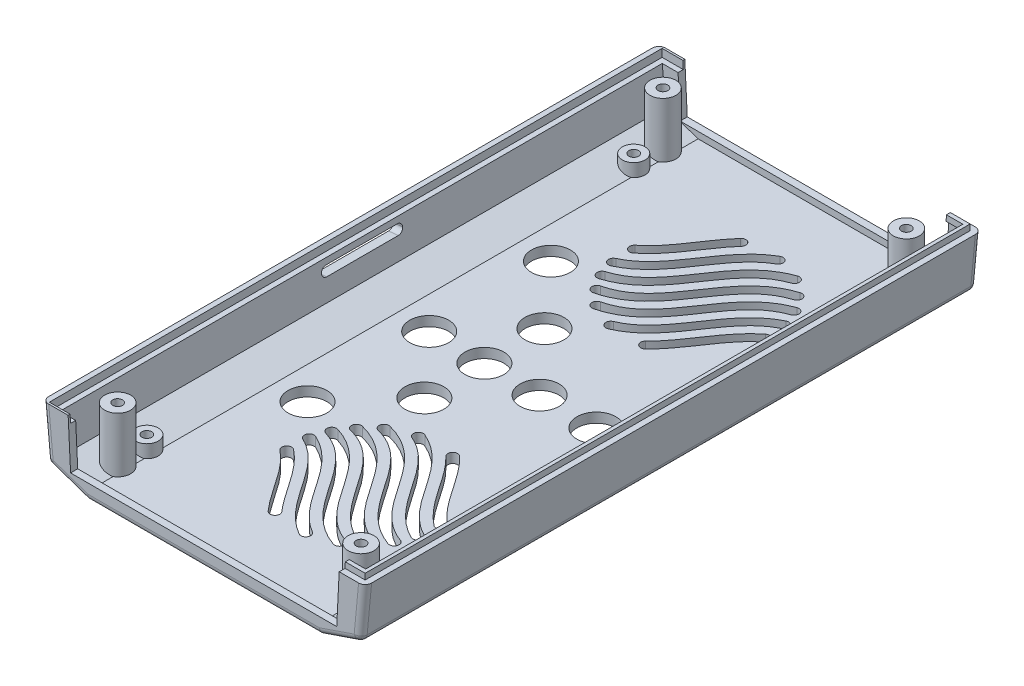
SolidWorks part; units mm, degrees
ref_plane "Спереди" through (0, 0, 0) normal (0, 0, 1) x (1, 0, 0)
ref_plane "Сверху" through (0, 0, 0) normal (0, 1, 0) x (1, 0, 0)
ref_plane "Справа" through (0, 0, 0) normal (1, 0, 0) x (0, 0, -1)
sketch "Эскиз1" plane through (0, 0, 0) normal (0, 0, 1) x (1, 0, 0)
  line L0 (-48.25, 4.1905) -> (-35.9646, 0)
  line L1 (48.25, 4.1905) -> (49.75, 20)
  line L2 (-48.25, 4.1905) -> (-49.75, 20)
  line L3 (-35.9646, 0) -> (35.9646, 0)
  line L4 (35.9646, 0) -> (48.25, 4.1905)
  line L5 (-49.75, 20) -> (49.75, 20) construction
  line L6 (45.4465, 6.404) -> (46.7634, 20.2834)
  line L7 (35.4671, 3) -> (45.4465, 6.404)
  line L8 (-35.4671, 3) -> (35.4671, 3)
  line L9 (-45.4465, 6.404) -> (-35.4671, 3)
  line L10 (-45.4465, 6.404) -> (-46.5088, 17.6)
  line L11 (49.75, 20) -> (47.95, 20)
  line L12 (47.95, 20) -> (47.95, 21.8)
  line L13 (46.7634, 20.2834) -> (46.9073, 21.8)
  line L14 (46.9073, 21.8) -> (47.95, 21.8)
  line L15 (-49.75, 20) -> (-48.15, 20)
  line L16 (-48.15, 20) -> (-48.15, 17.6)
  line L17 (-48.15, 17.6) -> (-46.5088, 17.6)
  line L20 (-45.4465, 6.404) -> (-46.7634, 20.2834) construction
  point P3 (0, 0)
  point P5 (0, 20)
  dimension "D1" = 99.5
  dimension "D2" = 20
  dimension "D3" = 96.5
  dimension "D4" = 3
  dimension "D5" = 1.8
  dimension "D6" = 1.8
  dimension "D7" = 2.4
  dimension "D8" = 1.6
extrude "Бобышка-Вытянуть1" add sketch "Эскиз1" along normal blind 92.8 and the other way blind 92.8
ref_plane "Плоскость смыкания" through (0, 20, 0) normal (0, 1, 0) x (-1, 0, 0)
ref_plane "Плоскость2" through (0, 0, -92.8) normal (0, 0, 1) x (1, 0, 0)
ref_plane "Плоскость3" through (0, 0, 92.8) normal (0, 0, 1) x (1, 0, 0)
ref_plane "Плоскость4" through (0, 3, 0) normal (0, 1, 0) x (-1, 0, 0)
sketch "Эскиз5" plane through (0, 0, 92.8) normal (0, 0, 1) x (1, 0, 0)
  line L0 (-48.25, 4.1905) -> (-35.9646, 0)
  line L1 (48.25, 4.1905) -> (49.75, 20)
  line L2 (-48.25, 4.1905) -> (-49.75, 20)
  line L3 (-35.9646, 0) -> (35.9646, 0)
  line L4 (35.9646, 0) -> (48.25, 4.1905)
  line L5 (-48.15, 20) -> (47.95, 20)
  line L11 (49.75, 20) -> (47.95, 20)
  line L15 (-49.75, 20) -> (-48.15, 20)
  point P3 (0, 0)
  point P6 (45.4465, 6.404)
  point P10 (46.7634, 20.2834)
  point P13 (-45.4465, 6.404)
  point P14 (-46.7634, 20.2834)
extrude "Бобышка-Вытянуть3" add sketch "Эскиз5" along normal blind 2.2
sketch "Эскиз9" plane through (0, 20, 0) normal (0, 1, 0) x (-1, 0, 0)
  line L0 (48.15, -92.8) -> (48.15, 92.8) construction
  line L1 (48.15, 92.8) -> (38.4865, 92.8)
  line L2 (48.15, 92.8) -> (48.15, 94.4)
  line L3 (48.15, 94.4) -> (38.4865, 94.4)
  line L4 (38.4865, 92.8) -> (38.4865, 94.4)
  dimension "D1" = 1.6
extrude "Вырез-Вытянуть3" cut sketch "Эскиз9" against normal blind 2.4
sketch "Эскиз10" plane through (0, 20, 0) normal (0, 1, 0) x (1, 0, 0)
  line L1 (47.95, -92) -> (32.5393, -92)
  line L2 (47.95, -92) -> (47.95, -93.2)
  line L3 (47.95, -93.2) -> (32.5393, -93.2)
  line L4 (32.5393, -92) -> (32.5393, -93.2)
  line L5 (47.95, 92.8) -> (47.95, -92.8) construction
  line L6 (47.95, 92.8) -> (47.95, -92.8) construction
  dimension "D1" = 1.2
extrude "Бобышка-Вытянуть4" add sketch "Эскиз10" along normal blind 1.8
sketch "Эскиз6" plane through (0, 0, 95) normal (0, 0, 1) x (1, 0, 0)
  line L0 (-41.75, 19.9919) -> (-41, 4.9919)
  line L2 (-41, 4.9919) -> (41, 4.9919)
  line L3 (41, 4.9919) -> (41.75, 19.9919)
  line L4 (41.75, 19.9919) -> (41.8404, 21.8)
  line L6 (32.5393, 21.8) -> (47.95, 21.8) construction
  line L7 (41.8404, 21.8) -> (-41.75, 21.8)
  line L8 (-41.75, 21.8) -> (-41.75, 19.9919)
  point P4 (0, 19.9919)
  point P7 (0, 4.9919)
  dimension "D1" = 83.5
  dimension "D2" = 82
  dimension "D3" = 15
extrude "Вырез-Вытянуть1" cut sketch "Эскиз6" against normal blind 3
mirror "Зеркальное отражение2" about plane through (0, 0, 0) normal (0, 0, 1) of "Вырез-Вытянуть1", "Бобышка-Вытянуть3", "Вырез-Вытянуть3", "Бобышка-Вытянуть4"
fillet "Скругление1" radius 2 12 edges at (48.25, 4.1905, 0) (-48.25, 4.1905, 0) (49, 12.0952, 95) (42.1073, 2.0952, 95) (0, 0, 95) (-42.1073, 2.0952, 95) (-49, 12.0952, 95) (-49, 12.0952, -95) (-42.1073, 2.0952, -95) (0, 0, -95) (42.1073, 2.0952, -95) (49, 12.0952, -95)
sketch "Эскиз12" plane through (0, 20, 0) normal (0, 1, 0) x (-1, 0, 0)
  circle A0 centre (37.5, -84) radius 4
  circle A1 centre (37.5, 84) radius 4
  circle A2 centre (-37.5, 84) radius 4
  circle A3 centre (-37.5, -84) radius 4
  circle A4 centre (37.5, -84) radius 1.5
  circle A5 centre (-37.5, -84) radius 1.5
  circle A6 centre (-37.5, 84) radius 1.5
  circle A7 centre (37.5, 84) radius 1.5
  dimension "D1" = 84
  dimension "D2" = 84
  dimension "D3" = 37.5
  dimension "D4" = 37.5
extrude "Бобышка-Вытянуть5" add sketch "Эскиз12" against normal blind 17
sketch "Эскиз13" plane through (0, 3, 0) normal (0, 1, 0) x (-1, 0, 0)
  circle A0 centre (37.5, -75) radius 3.5
  circle A1 centre (-37.5, -75) radius 3.5
  circle A2 centre (-37.5, 75) radius 3.5
  circle A3 centre (37.5, 75) radius 3.5
  circle A4 centre (37.5, -75) radius 1.5
  circle A5 centre (-37.5, -75) radius 1.5
  circle A6 centre (-37.5, 75) radius 1.5
  circle A7 centre (37.5, 75) radius 1.5
  dimension "D1" = 37.5
  dimension "D2" = 37.5
  dimension "D3" = 75
  dimension "D4" = 75
extrude "Бобышка-Вытянуть6" add sketch "Эскиз13" along normal blind 4
sketch "Эскиз14" plane through (-47.4255, -4.4997, 0) normal (-0.9955, -0.0945, 0) x (0, 0, 1)
  line L0 (-12.5, 18.6097) -> (12.5, 18.5897) construction
  line L1 (-11.01, 20.0997) -> (11.01, 20.0997)
  line L2 (-12.5, 18.6097) -> (-12.5, 18.5897)
  line L3 (-11.01, 17.0997) -> (11.01, 17.0997)
  line L4 (12.5, 18.6097) -> (12.5, 18.5897)
  line L5 (-93, 24.6097) -> (93, 24.6097) construction
  line L6 (0, 20.0997) -> (0, 17.0997) construction
  arc A0 (11.01, 20.0997) -> (12.5, 18.6097) centre (11.01, 18.6097) cw
  arc A1 (12.5, 18.5897) -> (11.01, 17.0997) centre (11.01, 18.5897) cw
  arc A2 (-11.01, 17.0997) -> (-12.5, 18.5897) centre (-11.01, 18.5897) cw
  arc A3 (-11.01, 20.0997) -> (-12.5, 18.6097) centre (-11.01, 18.6097) ccw
  point P4 (0, 17.0997)
  point P8 (12.5, 20.0997)
  point P13 (-12.5, 17.0997)
  point P16 (-12.5, 20.0997)
  point P19 (0, 24.6097)
  dimension "D3" = 1.49
  dimension "D1" = 25
  dimension "D2" = 3
  dimension "D4" = 6
extrude "Вырез-Вытянуть4" cut sketch "Эскиз14" against normal blind 3
sketch "Эскиз23" plane through (0, 0, 0) normal (0, -1, 0) x (1, 0, 0)
  line L0 (0, -93) -> (0, 93) construction
  line L1 (-35.9646, -93) -> (35.9646, -93) construction
  line L2 (35.9646, 93) -> (-35.9646, 93) construction
  line L3 (-49.75, 0) -> (49.75, 0) construction
  line L6 (-49.75, -93) -> (-49.75, 93) construction
  line L7 (49.75, -93) -> (49.75, 93) construction
  point P12 (0, 0)
sketch "Эскиз27" plane through (-36.5202, 0, -3.5105) normal (0, -1, 0) x (0, 0, 1)
  line L0 (3.5105, 0.9798) -> (3.5105, -74.0202) construction
  line L1 (-71.4995, -36.5202) -> (78.885, -36.5202) construction
  circle A0 centre (22.0105, -28.0202) radius 6
  circle A1 centre (-33.9895, -11.0202) radius 6
  circle A2 centre (3.5105, -11.0202) radius 6
  circle A3 centre (41.0105, -11.0202) radius 6
  circle A4 centre (54.5105, -42.5202) radius 25 construction
  circle A5 centre (-14.9895, -28.0202) radius 6
  circle A6 centre (3.5105, -28.0202) radius 6
  circle A7 centre (3.5105, -45.0202) radius 6
  circle A8 centre (3.5105, -62.5202) radius 6
  circle A9 centre (-47.4895, -42.5202) radius 25 construction
  arc A10 (-48.8656, -21.59) -> (-51.2327, -19.7469) centre (-50.0492, -20.6685) ccw
  arc A11 (-44.7101, -20.2817) -> (-41.9906, -21.5484) centre (-43.3503, -20.915) cw
  arc A12 (-39.5591, -22.1707) -> (-36.6947, -23.0625) centre (-38.1269, -22.6166) cw
  arc A13 (-34.9969, -25.2662) -> (-32.0843, -25.9852) centre (-33.5406, -25.6257) cw
  arc A14 (-30.7542, -29.5088) -> (-27.8417, -30.2278) centre (-29.298, -29.8683) cw
  arc A15 (-27.5032, -36.7235) -> (-24.7455, -37.9047) centre (-26.1244, -37.3141) cw
  arc A16 (-27.2708, -46.9318) -> (-25.0975, -48.9998) centre (-26.1841, -47.9658) cw
  arc A17 (-69.2669, -34.1546) -> (-67.2799, -36.4022) centre (-68.2734, -35.2784) ccw
  arc A18 (-70.5617, -45.0109) -> (-67.9586, -46.5021) centre (-69.2602, -45.7565) ccw
  arc A19 (-68.0072, -52.9601) -> (-65.174, -53.9464) centre (-66.5906, -53.4532) ccw
  arc A20 (-63.9746, -57.836) -> (-61.1135, -58.7384) centre (-62.544, -58.2872) ccw
  arc A21 (-59.4766, -61.3164) -> (-56.6494, -62.32) centre (-58.063, -61.8182) ccw
  arc A22 (-54.2329, -63.1869) -> (-51.5421, -64.5135) centre (-52.8875, -63.8502) ccw
  arc A23 (-47.5717, -63.5739) -> (-45.1994, -65.4101) centre (-46.3856, -64.492) ccw
  arc A24 (58.2537, -19.7469) -> (55.8866, -21.59) centre (57.0701, -20.6685) ccw
  arc A25 (49.0116, -21.5484) -> (51.731, -20.2817) centre (50.3713, -20.915) cw
  arc A26 (43.7157, -23.0625) -> (46.5801, -22.1707) centre (45.1479, -22.6166) cw
  arc A27 (39.1053, -25.9852) -> (42.0179, -25.2662) centre (40.5616, -25.6257) cw
  arc A28 (34.8627, -30.2278) -> (37.7752, -29.5088) centre (36.3189, -29.8683) cw
  arc A29 (31.7665, -37.9047) -> (34.5242, -36.7235) centre (33.1454, -37.3141) cw
  arc A30 (32.1184, -48.9998) -> (34.2918, -46.9318) centre (33.2051, -47.9658) cw
  arc A31 (76.2879, -34.1546) -> (74.3009, -36.4022) centre (75.2944, -35.2784) cw
  arc A32 (77.5827, -45.0109) -> (74.9796, -46.5021) centre (76.2811, -45.7565) cw
  arc A33 (75.0282, -52.9601) -> (72.1949, -53.9464) centre (73.6116, -53.4532) cw
  arc A34 (70.9955, -57.836) -> (68.1345, -58.7384) centre (69.565, -58.2872) cw
  arc A35 (66.4976, -61.3164) -> (63.6704, -62.32) centre (65.084, -61.8182) cw
  arc A36 (61.2539, -63.1869) -> (58.5631, -64.5135) centre (59.9085, -63.8502) cw
  arc A37 (54.5927, -63.5739) -> (52.2203, -65.4101) centre (53.4065, -64.492) cw
  spline S0 degree 3 poles (-62.544, -58.2872) (-57.6134, -42.6538) (-37.566, -41.9323) (-33.5406, -25.6257) knots 0 0 0 0 1 1 1 1 construction
  spline S1 degree 3 poles (-66.5906, -53.4532) (-64.9753, -48.8132) (-58.5281, -41.6719) (-45.7936, -34.5728) (-39.5897, -27.3147) (-38.1269, -22.6166) knots 0.012762 0.012762 0.012762 0.012762 0.316872 0.671472 0.974157 0.974157 0.974157 0.974157 construction
  spline S2 degree 3 poles (-69.2602, -45.7565) (-67.5896, -42.8402) (-61.6924, -36.8281) (-50.7993, -30.7556) (-44.9391, -24.3259) (-43.3503, -20.915) knots 0.094171 0.094171 0.094171 0.094171 0.316872 0.671472 0.916546 0.916546 0.916546 0.916546 construction
  spline S3 degree 3 poles (-68.2734, -35.2784) (-67.8647, -34.917) (-63.4796, -31.2167) (-56.4359, -27.29) (-51.3026, -22.2782) (-50.0492, -20.6685) knots 0.27954 0.27954 0.27954 0.27954 0.316872 0.671472 0.811315 0.811315 0.811315 0.811315 construction
  spline S4 degree 3 poles (-58.063, -61.8182) (-56.4384, -57.2414) (-46.7878, -46.5806) (-32.0478, -41.0078) (-29.298, -29.8683) knots 0.015397 0.015397 0.015397 0.015397 0.316872 1 1 1 1 construction
  spline S5 degree 3 poles (53.4065, -64.492) (52.0058, -62.6823) (46.6132, -57.5469) (38.7406, -53.1581) (34.0451, -48.8486) (33.2051, -47.9658) knots 0.161129 0.161129 0.161129 0.161129 0.316872 0.671472 0.755481 0.755481 0.755481 0.755481 construction
  spline S6 degree 3 poles (59.9085, -63.8502) (58.2051, -60.395) (52.1118, -54.0044) (40.6708, -47.6263) (34.7264, -41.0056) (33.1454, -37.3141) knots 0.066312 0.066312 0.066312 0.066312 0.316872 0.671472 0.930061 0.930061 0.930061 0.930061 construction
  spline S7 degree 3 poles (-52.8875, -63.8502) (-51.1841, -60.395) (-45.0908, -54.0044) (-33.6498, -47.6263) (-27.7054, -41.0056) (-26.1244, -37.3141) knots 0.066312 0.066312 0.066312 0.066312 0.316872 0.671472 0.930061 0.930061 0.930061 0.930061 construction
  spline S8 degree 3 poles (-46.3856, -64.492) (-44.9848, -62.6823) (-39.5922, -57.5469) (-31.7196, -53.1581) (-27.0241, -48.8486) (-26.1841, -47.9658) knots 0.161129 0.161129 0.161129 0.161129 0.316872 0.671472 0.755481 0.755481 0.755481 0.755481 construction
  spline S9 degree 3 poles (65.084, -61.8182) (63.4594, -57.2414) (53.8088, -46.5806) (39.0688, -41.0078) (36.3189, -29.8683) knots 0.015397 0.015397 0.015397 0.015397 0.316872 1 1 1 1 construction
  spline S10 degree 3 poles (69.565, -58.2872) (64.6344, -42.6538) (44.5869, -41.9323) (40.5616, -25.6257) knots 0 0 0 0 1 1 1 1 construction
  spline S11 degree 3 poles (73.6116, -53.4532) (71.9963, -48.8132) (65.549, -41.6719) (52.8146, -34.5728) (46.6107, -27.3147) (45.1479, -22.6166) knots 0.012762 0.012762 0.012762 0.012762 0.316872 0.671472 0.974157 0.974157 0.974157 0.974157 construction
  spline S12 degree 3 poles (76.2811, -45.7565) (74.6105, -42.8402) (68.7133, -36.8281) (57.8203, -30.7556) (51.9601, -24.3259) (50.3713, -20.915) knots 0.094171 0.094171 0.094171 0.094171 0.316872 0.671472 0.916546 0.916546 0.916546 0.916546 construction
  spline S13 degree 3 poles (75.2944, -35.2784) (74.8857, -34.917) (70.5006, -31.2167) (63.4568, -27.29) (58.3236, -22.2782) (57.0701, -20.6685) knots 0.27954 0.27954 0.27954 0.27954 0.316872 0.671472 0.811315 0.811315 0.811315 0.811315 construction
  spline S14 degree 1 poles (76.2879, -34.1546) (58.2537, -19.7469) knots 0 0 1 1 construction
  spline S15 degree 3 poles (76.2879, -34.1546) (74.7822, -32.8234) (71.5378, -30.397) (66.5901, -27.1252) (61.9517, -23.7407) (59.3755, -21.1877) (58.2537, -19.7469) knots 0.27954 0.27954 0.27954 0.27954 0.412484 0.545428 0.678371 0.811315 0.811315 0.811315 0.811315
  spline S16 degree 1 poles (77.5827, -45.0109) (51.731, -20.2817) knots 0 0 1 1 construction
  spline S17 degree 3 poles (77.5827, -45.0109) (77.1753, -44.2996) (76.2712, -42.9104) (74.259, -40.4246) (71.3962, -37.7193) (67.6619, -34.9224) (63.8374, -32.3466) (60.1279, -29.7894) (56.7346, -27.0652) (54.3221, -24.5063) (52.7236, -22.2082) (52.0339, -20.9319) (51.731, -20.2817) knots 0.094171 0.094171 0.094171 0.094171 0.145569 0.196968 0.299765 0.402562 0.505359 0.608156 0.710953 0.81375 0.865148 0.916546 0.916546 0.916546 0.916546
  spline S18 degree 1 poles (75.0282, -52.9601) (46.5801, -22.1707) knots 0 0 1 1 construction
  spline S19 degree 3 poles (75.0282, -52.9601) (74.8597, -52.4761) (74.4852, -51.5102) (73.6376, -49.7081) (72.3891, -47.6332) (70.6488, -45.4151) (68.075, -42.7623) (64.5099, -39.9123) (60.0298, -36.8804) (55.6747, -33.9037) (52.4176, -31.2208) (50.1795, -28.8143) (48.7144, -26.844) (47.6923, -25.0243) (47.0106, -23.4467) (46.7124, -22.5957) (46.5801, -22.1707) knots 0.012762 0.012762 0.012762 0.012762 0.042805 0.072849 0.132936 0.193023 0.25311 0.373285 0.493459 0.613633 0.733808 0.793895 0.853982 0.914069 0.944113 0.974157 0.974157 0.974157 0.974157
  spline S20 degree 1 poles (70.9955, -57.836) (42.0179, -25.2662) knots 0 0 1 1 construction
  spline S21 degree 3 poles (70.9955, -57.836) (70.8333, -57.3215) (70.4675, -56.293) (69.6256, -54.3805) (68.3627, -52.1843) (66.5775, -49.8483) (63.9161, -47.0686) (60.2066, -44.1046) (55.5421, -40.962) (51.0318, -37.8603) (47.7027, -35.0326) (45.456, -32.4686) (44.0111, -30.3535) (43.0304, -28.3827) (42.3992, -26.6645) (42.1325, -25.7305) (42.0179, -25.2662) knots 0 0 0 0 0.03125 0.0625 0.125 0.1875 0.25 0.375 0.5 0.625 0.75 0.8125 0.875 0.9375 0.96875 1 1 1 1
  spline S22 degree 1 poles (66.4976, -61.3164) (37.7752, -29.5088) knots 0 0 1 1 construction
  spline S23 degree 3 poles (66.4976, -61.3164) (66.3225, -60.8232) (65.9331, -59.8393) (65.052, -58.0067) (63.7547, -55.9012) (61.9494, -53.6562) (59.2848, -50.9758) (55.6067, -48.0976) (51.0144, -45.0161) (46.5933, -41.9535) (43.3384, -39.1541) (41.1423, -36.6171) (39.7295, -34.5261) (38.7693, -32.5803) (38.1502, -30.886) (37.8881, -29.9661) (37.7752, -29.5088) knots 0.015397 0.015397 0.015397 0.015397 0.046166 0.076934 0.138472 0.20001 0.261548 0.384623 0.507698 0.630774 0.753849 0.815387 0.876925 0.938462 0.969231 1 1 1 1
  spline S24 degree 1 poles (61.2539, -63.1869) (34.5242, -36.7235) knots 0 0 1 1 construction
  spline S25 degree 3 poles (61.2539, -63.1869) (60.8672, -62.4026) (59.9869, -60.8636) (57.9783, -58.1353) (55.0438, -55.1959) (51.1506, -52.2088) (47.1305, -49.4935) (43.2218, -46.8136) (39.6577, -43.9534) (37.1507, -41.2457) (35.5174, -38.7959) (34.8232, -37.4216) (34.5242, -36.7235) knots 0.066312 0.066312 0.066312 0.066312 0.120297 0.174281 0.28225 0.390218 0.498187 0.606155 0.714124 0.822092 0.876076 0.930061 0.930061 0.930061 0.930061
  spline S26 degree 1 poles (54.5927, -63.5739) (34.2918, -46.9318) knots 0 0 1 1 construction
  spline S27 degree 3 poles (54.5927, -63.5739) (53.8894, -62.6652) (52.3425, -60.9377) (48.9659, -57.9294) (44.3669, -54.7036) (39.815, -51.674) (36.4928, -49.0678) (35, -47.6761) (34.2918, -46.9318) knots 0.161129 0.161129 0.161129 0.161129 0.235423 0.309717 0.458305 0.606893 0.681187 0.755481 0.755481 0.755481 0.755481
  spline S28 degree 1 poles (-67.2799, -36.4022) (-48.8656, -21.59) knots 0 0 1 1 construction
  spline S29 degree 3 poles (-67.2799, -36.4022) (-66.5757, -35.7796) (-65.1274, -34.6014) (-62.0122, -32.3385) (-57.8995, -29.617) (-53.8391, -26.6646) (-50.8629, -23.9397) (-49.4942, -22.3973) (-48.8656, -21.59) knots 0.27954 0.27954 0.27954 0.27954 0.346012 0.412484 0.545428 0.678371 0.744843 0.811315 0.811315 0.811315 0.811315
  spline S30 degree 1 poles (-67.9586, -46.5021) (-41.9906, -21.5484) knots 0 0 1 1 construction
  spline S31 degree 3 poles (-67.9586, -46.5021) (-67.6048, -45.8845) (-66.8234, -44.6836) (-65.0533, -42.4942) (-62.4638, -40.0398) (-58.9274, -37.3859) (-55.1526, -34.8428) (-51.3411, -32.2173) (-47.6997, -29.3015) (-44.9865, -26.4335) (-43.1446, -23.7879) (-42.3421, -22.3029) (-41.9906, -21.5484) knots 0.094171 0.094171 0.094171 0.094171 0.145569 0.196968 0.299765 0.402562 0.505359 0.608156 0.710953 0.81375 0.865148 0.916546 0.916546 0.916546 0.916546
  spline S32 degree 1 poles (-65.174, -53.9464) (-36.6947, -23.0625) knots 0 0 1 1 construction
  spline S33 degree 3 poles (-65.174, -53.9464) (-65.0283, -53.5279) (-64.7041, -52.6919) (-63.9733, -51.1383) (-62.8948, -49.3446) (-61.3696, -47.3984) (-59.0625, -45.0174) (-55.7431, -42.3552) (-51.3563, -39.3835) (-46.8876, -36.3328) (-43.3681, -33.4441) (-40.8548, -30.7455) (-39.173, -28.4863) (-37.985, -26.3725) (-37.1925, -24.538) (-36.8479, -23.5545) (-36.6947, -23.0625) knots 0.012762 0.012762 0.012762 0.012762 0.042805 0.072849 0.132936 0.193023 0.25311 0.373285 0.493459 0.613633 0.733808 0.793895 0.853982 0.914069 0.944113 0.974157 0.974157 0.974157 0.974157
  spline S34 degree 1 poles (-61.1135, -58.7384) (-32.0843, -25.9852) knots 0 0 1 1 construction
  spline S35 degree 3 poles (-61.1135, -58.7384) (-60.9729, -58.2928) (-60.6556, -57.4006) (-59.9295, -55.7516) (-58.84, -53.8556) (-57.279, -51.8105) (-54.8979, -49.32) (-51.4455, -46.5515) (-46.8704, -43.4663) (-42.2261, -40.277) (-38.6053, -37.2144) (-36.0642, -34.3189) (-34.3962, -31.8796) (-33.2545, -29.5862) (-32.5226, -27.5927) (-32.2163, -26.5197) (-32.0843, -25.9852) knots 0 0 0 0 0.03125 0.0625 0.125 0.1875 0.25 0.375 0.5 0.625 0.75 0.8125 0.875 0.9375 0.96875 1 1 1 1
  spline S36 degree 1 poles (-56.6494, -62.32) (-27.8417, -30.2278) knots 0 0 1 1 construction
  spline S37 degree 3 poles (-56.6494, -62.32) (-56.4981, -61.8936) (-56.1612, -61.0425) (-55.4015, -59.4626) (-54.2801, -57.6411) (-52.6947, -55.6672) (-50.2987, -53.2537) (-46.8593, -50.5534) (-42.3398, -47.5186) (-37.7748, -44.3611) (-34.2269, -41.3224) (-31.74, -38.4537) (-30.1081, -36.0408) (-28.9905, -33.7765) (-28.2727, -31.8109) (-27.9716, -30.7543) (-27.8417, -30.2278) knots 0.015397 0.015397 0.015397 0.015397 0.046166 0.076934 0.138472 0.20001 0.261548 0.384623 0.507698 0.630774 0.753849 0.815387 0.876925 0.938462 0.969231 1 1 1 1
  spline S38 degree 1 poles (-51.5421, -64.5135) (-24.7455, -37.9047) knots 0 0 1 1 construction
  spline S39 degree 3 poles (-51.5421, -64.5135) (-51.2078, -63.8353) (-50.449, -62.5086) (-48.6962, -60.125) (-46.0657, -57.4808) (-42.4026, -54.6635) (-38.4498, -51.9922) (-34.441, -49.2459) (-30.6151, -46.1843) (-27.7877, -43.1424) (-25.9005, -40.3143) (-25.0927, -38.7153) (-24.7455, -37.9047) knots 0.066312 0.066312 0.066312 0.066312 0.120297 0.174281 0.28225 0.390218 0.498187 0.606155 0.714124 0.822092 0.876076 0.930061 0.930061 0.930061 0.930061
  spline S40 degree 1 poles (-45.1994, -65.4101) (-25.0975, -48.9998) knots 0 0 1 1 construction
  spline S41 degree 3 poles (-45.1994, -65.4101) (-43.941, -63.7844) (-41.0042, -60.9429) (-35.7069, -57.2147) (-31.0701, -54.1321) (-27.5385, -51.3677) (-25.8766, -49.8186) (-25.0975, -48.9998) knots 0.161129 0.161129 0.161129 0.161129 0.309717 0.458305 0.606893 0.681187 0.755481 0.755481 0.755481 0.755481
  spline S42 degree 1 poles (74.3009, -36.4022) (55.8866, -21.59) knots 0 0 1 1 construction
  spline S43 degree 3 poles (74.3009, -36.4022) (73.5966, -35.7796) (72.1484, -34.6014) (69.0331, -32.3385) (64.9204, -29.617) (60.8601, -26.6646) (57.8839, -23.9397) (56.5152, -22.3973) (55.8866, -21.59) knots 0.27954 0.27954 0.27954 0.27954 0.346012 0.412484 0.545428 0.678371 0.744843 0.811315 0.811315 0.811315 0.811315
  spline S44 degree 1 poles (74.9796, -46.5021) (49.0116, -21.5484) knots 0 0 1 1 construction
  spline S45 degree 3 poles (74.9796, -46.5021) (74.6258, -45.8845) (73.8444, -44.6836) (72.0743, -42.4942) (69.4848, -40.0398) (65.9484, -37.3859) (62.1736, -34.8428) (58.3621, -32.2173) (54.7207, -29.3015) (52.0075, -26.4335) (50.1656, -23.7879) (49.3631, -22.3029) (49.0116, -21.5484) knots 0.094171 0.094171 0.094171 0.094171 0.145569 0.196968 0.299765 0.402562 0.505359 0.608156 0.710953 0.81375 0.865148 0.916546 0.916546 0.916546 0.916546
  spline S46 degree 1 poles (72.1949, -53.9464) (43.7157, -23.0625) knots 0 0 1 1 construction
  spline S47 degree 3 poles (72.1949, -53.9464) (72.0492, -53.5279) (71.7251, -52.6919) (70.9943, -51.1383) (69.9157, -49.3446) (68.3905, -47.3984) (66.0835, -45.0174) (62.7641, -42.3552) (58.3772, -39.3835) (53.9086, -36.3328) (50.3891, -33.4441) (47.8758, -30.7455) (46.194, -28.4863) (45.0059, -26.3725) (44.2135, -24.538) (43.8689, -23.5545) (43.7157, -23.0625) knots 0.012762 0.012762 0.012762 0.012762 0.042805 0.072849 0.132936 0.193023 0.25311 0.373285 0.493459 0.613633 0.733808 0.793895 0.853982 0.914069 0.944113 0.974157 0.974157 0.974157 0.974157
  spline S48 degree 1 poles (68.1345, -58.7384) (39.1053, -25.9852) knots 0 0 1 1 construction
  spline S49 degree 3 poles (68.1345, -58.7384) (67.9939, -58.2928) (67.6766, -57.4006) (66.9505, -55.7516) (65.861, -53.8556) (64.2999, -51.8105) (61.9189, -49.32) (58.4664, -46.5515) (53.8914, -43.4663) (49.247, -40.277) (45.6263, -37.2144) (43.0851, -34.3189) (41.4172, -31.8796) (40.2755, -29.5862) (39.5436, -27.5927) (39.2373, -26.5197) (39.1053, -25.9852) knots 0 0 0 0 0.03125 0.0625 0.125 0.1875 0.25 0.375 0.5 0.625 0.75 0.8125 0.875 0.9375 0.96875 1 1 1 1
  spline S50 degree 1 poles (63.6704, -62.32) (34.8627, -30.2278) knots 0 0 1 1 construction
  spline S51 degree 3 poles (63.6704, -62.32) (63.5191, -61.8936) (63.1822, -61.0425) (62.4225, -59.4626) (61.3011, -57.6411) (59.7157, -55.6672) (57.3197, -53.2537) (53.8803, -50.5534) (49.3608, -47.5186) (44.7958, -44.3611) (41.2479, -41.3224) (38.761, -38.4537) (37.1291, -36.0408) (36.0115, -33.7765) (35.2937, -31.8109) (34.9926, -30.7543) (34.8627, -30.2278) knots 0.015397 0.015397 0.015397 0.015397 0.046166 0.076934 0.138472 0.20001 0.261548 0.384623 0.507698 0.630774 0.753849 0.815387 0.876925 0.938462 0.969231 1 1 1 1
  spline S52 degree 1 poles (58.5631, -64.5135) (31.7665, -37.9047) knots 0 0 1 1 construction
  spline S53 degree 3 poles (58.5631, -64.5135) (58.2288, -63.8353) (57.47, -62.5086) (55.7172, -60.125) (53.0867, -57.4808) (49.4236, -54.6635) (45.4708, -51.9922) (41.4619, -49.2459) (37.636, -46.1843) (34.8086, -43.1424) (32.9215, -40.3143) (32.1137, -38.7153) (31.7665, -37.9047) knots 0.066312 0.066312 0.066312 0.066312 0.120297 0.174281 0.28225 0.390218 0.498187 0.606155 0.714124 0.822092 0.876076 0.930061 0.930061 0.930061 0.930061
  spline S54 degree 1 poles (52.2203, -65.4101) (32.1184, -48.9998) knots 0 0 1 1 construction
  spline S55 degree 3 poles (52.2203, -65.4101) (50.962, -63.7844) (48.0252, -60.9429) (42.7279, -57.2147) (38.0911, -54.1321) (34.5595, -51.3677) (32.8976, -49.8186) (32.1184, -48.9998) knots 0.161129 0.161129 0.161129 0.161129 0.309717 0.458305 0.606893 0.681187 0.755481 0.755481 0.755481 0.755481
  spline S56 degree 1 poles (-69.2669, -34.1546) (-51.2327, -19.7469) knots 0 0 1 1 construction
  spline S57 degree 3 poles (-69.2669, -34.1546) (-67.7612, -32.8234) (-64.5169, -30.397) (-59.5691, -27.1252) (-54.9307, -23.7407) (-52.3546, -21.1877) (-51.2327, -19.7469) knots 0.27954 0.27954 0.27954 0.27954 0.412484 0.545428 0.678371 0.811315 0.811315 0.811315 0.811315
  spline S58 degree 1 poles (-70.5617, -45.0109) (-44.7101, -20.2817) knots 0 0 1 1 construction
  spline S59 degree 3 poles (-70.5617, -45.0109) (-70.1543, -44.2996) (-69.2503, -42.9104) (-67.238, -40.4246) (-64.3753, -37.7193) (-60.6409, -34.9224) (-56.8164, -32.3466) (-53.107, -29.7894) (-49.7136, -27.0652) (-47.3011, -24.5063) (-45.7026, -22.2082) (-45.0129, -20.9319) (-44.7101, -20.2817) knots 0.094171 0.094171 0.094171 0.094171 0.145569 0.196968 0.299765 0.402562 0.505359 0.608156 0.710953 0.81375 0.865148 0.916546 0.916546 0.916546 0.916546
  spline S60 degree 1 poles (-68.0072, -52.9601) (-39.5591, -22.1707) knots 0 0 1 1 construction
  spline S61 degree 3 poles (-68.0072, -52.9601) (-67.8387, -52.4761) (-67.4642, -51.5102) (-66.6166, -49.7081) (-65.3681, -47.6332) (-63.6279, -45.4151) (-61.054, -42.7623) (-57.4889, -39.9123) (-53.0089, -36.8804) (-48.6538, -33.9037) (-45.3966, -31.2208) (-43.1585, -28.8143) (-41.6934, -26.844) (-40.6713, -25.0243) (-39.9896, -23.4467) (-39.6914, -22.5957) (-39.5591, -22.1707) knots 0.012762 0.012762 0.012762 0.012762 0.042805 0.072849 0.132936 0.193023 0.25311 0.373285 0.493459 0.613633 0.733808 0.793895 0.853982 0.914069 0.944113 0.974157 0.974157 0.974157 0.974157
  spline S62 degree 1 poles (-63.9746, -57.836) (-34.9969, -25.2662) knots 0 0 1 1 construction
  spline S63 degree 3 poles (-63.9746, -57.836) (-63.8123, -57.3215) (-63.4465, -56.293) (-62.6046, -54.3805) (-61.3417, -52.1843) (-59.5566, -49.8483) (-56.8951, -47.0686) (-53.1856, -44.1046) (-48.5211, -40.962) (-44.0108, -37.8603) (-40.6818, -35.0326) (-38.435, -32.4686) (-36.9902, -30.3535) (-36.0094, -28.3827) (-35.3782, -26.6645) (-35.1115, -25.7305) (-34.9969, -25.2662) knots 0 0 0 0 0.03125 0.0625 0.125 0.1875 0.25 0.375 0.5 0.625 0.75 0.8125 0.875 0.9375 0.96875 1 1 1 1
  spline S64 degree 1 poles (-59.4766, -61.3164) (-30.7542, -29.5088) knots 0 0 1 1 construction
  spline S65 degree 3 poles (-59.4766, -61.3164) (-59.3015, -60.8232) (-58.9122, -59.8393) (-58.031, -58.0067) (-56.7337, -55.9012) (-54.9284, -53.6562) (-52.2638, -50.9758) (-48.5857, -48.0976) (-43.9934, -45.0161) (-39.5723, -41.9535) (-36.3174, -39.1541) (-34.1214, -36.6171) (-32.7085, -34.5261) (-31.7483, -32.5803) (-31.1292, -30.886) (-30.8671, -29.9661) (-30.7542, -29.5088) knots 0.015397 0.015397 0.015397 0.015397 0.046166 0.076934 0.138472 0.20001 0.261548 0.384623 0.507698 0.630774 0.753849 0.815387 0.876925 0.938462 0.969231 1 1 1 1
  spline S66 degree 1 poles (-54.2329, -63.1869) (-27.5032, -36.7235) knots 0 0 1 1 construction
  spline S67 degree 3 poles (-54.2329, -63.1869) (-53.8462, -62.4026) (-52.9659, -60.8636) (-50.9573, -58.1353) (-48.0228, -55.1959) (-44.1296, -52.2088) (-40.1095, -49.4935) (-36.2008, -46.8136) (-32.6368, -43.9534) (-30.1297, -41.2457) (-28.4964, -38.7959) (-27.8022, -37.4216) (-27.5032, -36.7235) knots 0.066312 0.066312 0.066312 0.066312 0.120297 0.174281 0.28225 0.390218 0.498187 0.606155 0.714124 0.822092 0.876076 0.930061 0.930061 0.930061 0.930061
  spline S68 degree 1 poles (-47.5717, -63.5739) (-27.2708, -46.9318) knots 0 0 1 1 construction
  spline S69 degree 3 poles (-47.5717, -63.5739) (-46.8685, -62.6652) (-45.3215, -60.9377) (-41.9449, -57.9294) (-37.3459, -54.7036) (-32.7941, -51.674) (-29.4718, -49.0678) (-27.979, -47.6761) (-27.2708, -46.9318) knots 0.161129 0.161129 0.161129 0.161129 0.235423 0.309717 0.458305 0.606893 0.681187 0.755481 0.755481 0.755481 0.755481
  point P30 (3.5105, 12.9798)
  point P33 (3.5105, -36.5202)
  dimension "D11" = 12
  dimension "D3" = 51
  dimension "D4" = 37.5
  dimension "D5" = 18.5
  dimension "D6" = 6
  dimension "D7" = 8.5
  dimension "D8" = 8.5
  dimension "D9" = 26
  dimension "D10" = 25.5
  dimension "D2" = 1.5
  dimension "D12" = 1.5
extrude "Вырез-Вытянуть5" cut sketch "Эскиз27" against normal blind 4
sketch "Эскиз28" plane through (-47.4255, -4.4997, 0) normal (-0.9955, -0.0945, 0) x (0, 0, 1)
  line L0 (-12.5, 18.6097) -> (12.5, 18.6097) construction
  line L1 (0, 20.0997) -> (0, 17.0997) construction
  line L2 (11.01, 20.0997) -> (-11.01, 20.0997) construction
  line L3 (-11.01, 17.0997) -> (11.01, 17.0997) construction
